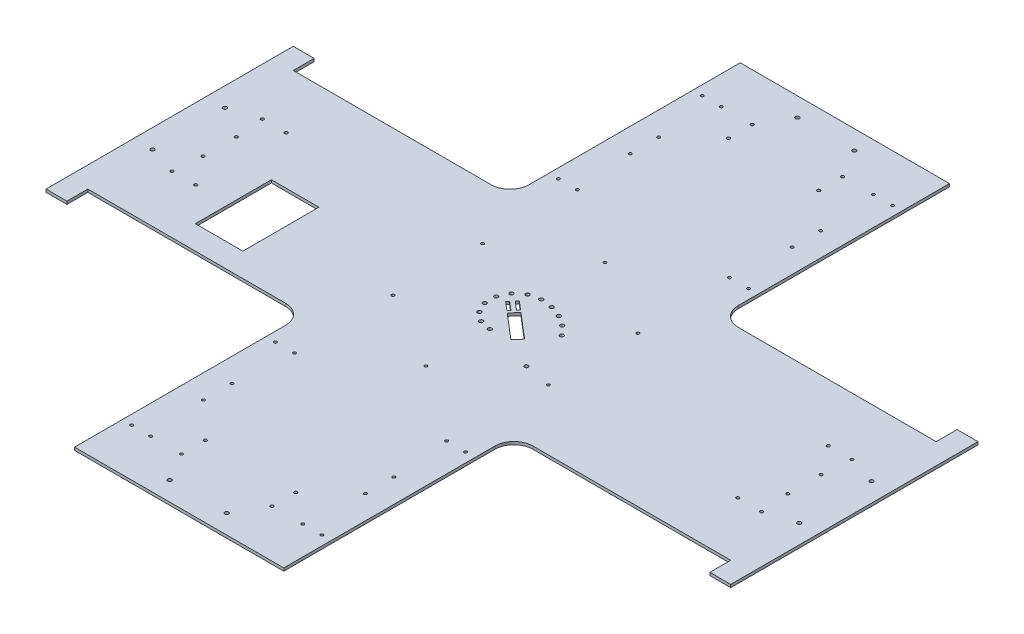
SolidWorks part; units mm, degrees
ref_plane "Front Plane" through (0, 0, 0) normal (0, 0, 1) x (1, 0, 0)
ref_plane "Top Plane" through (0, 0, 0) normal (0, 1, 0) x (1, 0, 0)
ref_plane "Right Plane" through (0, 0, 0) normal (1, 0, 0) x (0, 0, -1)
sketch "Sketch1" plane through (0, 0, 0) normal (0, 1, 0) x (1, 0, 0)
  line L0 (-110, 350) -> (-110, 108)
  line L1 (-110, 108) -> (-338, 108)
  line L2 (-338, 108) -> (-338, 130)
  line L3 (-338, 130) -> (-360, 130)
  line L4 (-360, 130) -> (-360, -130)
  line L5 (-360, 0) -> (1003.1457, 0) construction
  line L6 (0, 350) -> (0, -620.7989) construction
  line L7 (-338, -130) -> (-360, -130)
  line L8 (-338, -108) -> (-338, -130)
  line L9 (-110, -108) -> (-338, -108)
  line L10 (-110, 350) -> (110, 350)
  line L11 (-110, -350) -> (-110, -108)
  line L12 (-110, -350) -> (110, -350)
  line L13 (110, -350) -> (110, -108)
  line L14 (110, -108) -> (338, -108)
  line L15 (338, -108) -> (338, -130)
  line L16 (338, -130) -> (360, -130)
  line L17 (360, 130) -> (360, -130)
  line L18 (338, 130) -> (360, 130)
  line L19 (338, 108) -> (338, 130)
  line L20 (110, 108) -> (338, 108)
  line L21 (110, 350) -> (110, 108)
  point P17 (0, -350)
  dimension "D1" = 110
  dimension "D2" = 22
  dimension "D3" = 22
  dimension "D4" = 242
  dimension "D5" = 130
  dimension "D6" = 250
  dimension "D7" = 110
  dimension "D8" = 108
extrude "Boss-Extrude1" add sketch "Sketch1" along normal blind 3
sketch "Sketch2" plane through (0, 3, 0) normal (0, 1, 0) x (1, 0, 0)
  line L0 (360, -130) -> (360, 130) construction
  line L2 (338, 108) -> (110, 108) construction
  line L4 (0, 107.9437) -> (0, -458.275) construction
  line L5 (110, 108) -> (110, 350) construction
  line L6 (110, 350) -> (-110, 350) construction
  line L7 (-540.1841, 0) -> (-80.3508, 0) construction
  circle A0 centre (310, 47.5) radius 1.6
  circle A1 centre (285, 47.5) radius 1.6
  circle A2 centre (307.5, 17.5) radius 1.6
  circle A3 centre (307.5, -17.5) radius 1.6
  circle A4 centre (310, -47.5) radius 1.6
  circle A5 centre (285, -47.5) radius 1.6
  circle A6 centre (-285, -47.5) radius 1.6
  circle A7 centre (-310, -47.5) radius 1.6
  circle A8 centre (-307.5, -17.5) radius 1.6
  circle A9 centre (-307.5, 17.5) radius 1.6
  circle A10 centre (-285, 47.5) radius 1.6
  circle A11 centre (-310, 47.5) radius 1.6
  circle A13 centre (47.5, 300) radius 1.6
  circle A15 centre (47.5, 275) radius 1.6
  circle A16 centre (-47.5, 275) radius 1.6
  circle A17 centre (-47.5, 300) radius 1.6
  circle A18 centre (-47.5, -300) radius 1.6
  circle A19 centre (-47.5, -275) radius 1.6
  circle A20 centre (47.5, -275) radius 1.6
  circle A21 centre (47.5, -300) radius 1.6
  dimension "D1" = 3.2
  dimension "D2" = 3.2
  dimension "D3" = 3.2
  dimension "D4" = 3.2
  dimension "D5" = 3.2
  dimension "D6" = 3.2
  dimension "D15" = 3.2
  dimension "D16" = 3.2
  dimension "D7" = 50
  dimension "D8" = 25
  dimension "D9" = 95
  dimension "D10" = 35
  dimension "D11" = 60.5
  dimension "D12" = 90.5
  dimension "D13" = 52.5
  dimension "D14" = 110
  dimension "D17" = 50
  dimension "D18" = 25
  dimension "D19" = 62.5
  dimension "D20" = 108
extrude "Cut-Extrude1" cut sketch "Sketch2" against normal through all
sketch "Sketch3" plane through (0, 3, 0) normal (0, 1, 0) x (1, 0, 0)
  line L0 (360, -130) -> (360, 130) construction
  line L1 (338, 108) -> (110, 108) construction
  line L2 (-553.4456, 0) -> (-91.4299, 0) construction
  line L3 (0, 286.895) -> (0, -255.8046) construction
  line L4 (110, 108) -> (110, 350) construction
  line L5 (110, 350) -> (-110, 350) construction
  line L6 (-110, 350) -> (-110, 108) construction
  circle A0 centre (340, 38) radius 2
  circle A2 centre (340, -38) radius 2
  circle A3 centre (-340, -38) radius 2
  circle A4 centre (-340, 38) radius 2
  circle A5 centre (-30, 330) radius 2
  circle A7 centre (30, 330) radius 2
  circle A8 centre (30, -330) radius 2
  circle A9 centre (-30, -330) radius 2
  dimension "D1" = 4
  dimension "D6" = 4
  dimension "D7" = 80
  dimension "D2" = 20
  dimension "D3" = 70
  dimension "D4" = 108
  dimension "D5" = 110
  dimension "D8" = 20
extrude "Cut-Extrude2" cut sketch "Sketch3" against normal through all
sketch "Sketch4" plane through (0, 3, 0) normal (0, 1, 0) x (1, 0, 0)
  line L0 (0.8085, 29.8301) -> (-10.8593, 27.1789) construction
  line L1 (-10.8593, 27.1789) -> (-20.2814, 19.6888) construction
  line L2 (-20.2814, 19.6888) -> (-25.5122, 8.8484) construction
  line L3 (-25.5122, 8.8484) -> (-25.5122, -3.1881) construction
  line L4 (-25.5122, -3.1881) -> (-20.2814, -14.0285) construction
  line L5 (-20.2814, -14.0285) -> (-10.8593, -21.5186) construction
  line L6 (-10.8593, -21.5186) -> (0.8815, -24.1698) construction
  line L7 (0.8085, 29.8301) -> (13.3461, 28.3304) construction
  line L8 (13.3461, 28.3304) -> (25.203, 23.9881) construction
  line L9 (25.203, 23.9881) -> (35.7602, 17.0608) construction
  line L10 (35.7602, 17.0608) -> (44.4635, 7.9124) construction
  line L11 (44.4635, 7.9124) -> (53.9283, -38.7532) construction
  line L12 (0.8085, 2.8301) -> (0.8085, 97.0801) construction
  line L13 (0.8085, 2.8301) -> (0.8085, 97.0801) construction
  line L14 (0.8085, 2.8301) -> (82.4314, 49.9551) construction
  line L15 (-4.5918, -0.4234) -> (21.6669, -22.8005)
  line L16 (21.6669, -22.8005) -> (28.2827, -15.037)
  line L17 (-4.5918, -0.4234) -> (2.0241, 7.3401)
  line L18 (2.0241, 7.3401) -> (28.2827, -15.037)
  line L19 (-6.8751, 1.5225) -> (-4.9293, 3.8058)
  line L20 (-4.9293, 3.8058) -> (-14.0627, 11.5892)
  line L21 (-14.0627, 11.5892) -> (-16.0085, 9.3058)
  line L22 (-16.0085, 9.3058) -> (-6.8751, 1.5225)
  line L23 (2.0241, 7.3401) -> (0.8085, 2.8301) construction
  line L24 (-2.2051, 7.0025) -> (-0.2593, 9.2859)
  line L25 (-0.2593, 9.2859) -> (-9.3927, 17.0692)
  line L26 (-9.3927, 17.0692) -> (-11.3385, 14.7859)
  line L27 (-11.3385, 14.7859) -> (-2.2051, 7.0025)
  line L28 (0.8085, 2.8301) -> (48.4037, 2.8301) construction
  line L29 (0.8085, 2.8301) -> (0.8085, -17.1699) construction
  circle A0 centre (0.8085, 29.8301) radius 2
  circle A1 centre (13.3461, 28.3304) radius 2
  circle A2 centre (25.203, 23.9881) radius 2
  circle A3 centre (35.7602, 17.0608) radius 2
  circle A4 centre (44.4635, 7.9124) radius 2
  circle A5 centre (53.9283, -38.7532) radius 2
  circle A6 centre (0.8085, 2.8301) radius 135 construction
  circle A7 centre (-10.8593, 27.1789) radius 2
  circle A8 centre (-20.2814, 19.6888) radius 2
  circle A9 centre (-25.5122, 8.8484) radius 2
  circle A10 centre (-25.5122, -3.1881) radius 2
  circle A11 centre (-20.2814, -14.0285) radius 2
  circle A12 centre (-10.8593, -21.5186) radius 2
  circle A13 centre (0.8815, -24.1698) radius 2
  circle A14 centre (0.8085, 2.8301) radius 27 construction
  circle A15 centre (0.8085, 2.8301) radius 28.4158 construction
  circle A16 centre (0.8085, 2.8301) radius 32.2916 construction
  circle A17 centre (0.8085, 2.8301) radius 37.7377 construction
  circle A18 centre (0.8085, 2.8301) radius 43.9498 construction
  circle A19 centre (0.8085, 2.8301) radius 67.4602 construction
  circle A20 centre (0.8085, 2.8301) radius 94.25 construction
  circle A21 centre (0.8085, 97.0801) radius 1.5
  circle A22 centre (82.4314, 49.9551) radius 1.5
  circle A23 centre (82.4314, -44.2949) radius 1.5
  circle A24 centre (0.8085, -91.4199) radius 1.5
  circle A25 centre (-80.8144, -44.2949) radius 1.5
  circle A26 centre (-80.8144, 49.9551) radius 1.5
  point P32 (0.8085, 2.8301)
  dimension "D1" = 4
  dimension "D2" = 270
  dimension "D3" = 54
  dimension "D12" = 188.5
  dimension "D13" = 3
  dimension "D4" = 11.9653
  dimension "D5" = 12.627
  dimension "D6" = 47.6157
  dimension "D8" = 60.7074
  dimension "D9" = 70.0293
  dimension "D10" = 81.6875
  dimension "D14" = 60
  dimension "D15" = 34.5
  dimension "D16" = 10.2
  dimension "D17" = 12
  dimension "D18" = 3
  dimension "D19" = 3
  dimension "D20" = 4.6709
  dimension "D21" = 3
  dimension "D22" = 20
  dimension "D23" = 130.437
  dimension "D24" = 5.4003
extrude "Cut-Extrude3" cut sketch "Sketch4" against normal blind 10
sketch "Sketch5" plane through (0, 3, 0) normal (0, 1, 0) x (1, 0, 0)
  line L0 (110, 350) -> (-110, 350) construction
  line L1 (110, 108) -> (110, 350) construction
  line L2 (0, 224.365) -> (185.6725, 224.365) construction
  line L3 (90, 361.0488) -> (90, 126.2188) construction
  line L4 (0, 375.894) -> (0, 88.4107) construction
  line L5 (349.7475, 0) -> (-242.2654, 0) construction
  circle A0 centre (80, 300) radius 1.5
  circle A1 centre (80, 148.73) radius 1.5
  circle A2 centre (85.11, 239.365) radius 1.5
  circle A3 centre (85.11, 209.365) radius 1.5
  circle A4 centre (100, 148.73) radius 1.5
  circle A5 centre (100, 300) radius 1.5
  circle A6 centre (-100, 300) radius 1.5
  circle A7 centre (-100, 148.73) radius 1.5
  circle A8 centre (-85.11, 209.365) radius 1.5
  circle A9 centre (-85.11, 239.365) radius 1.5
  circle A10 centre (-80, 148.73) radius 1.5
  circle A11 centre (-80, 300) radius 1.5
  circle A12 centre (-80, -300) radius 1.5
  circle A13 centre (-80, -148.73) radius 1.5
  circle A14 centre (-85.11, -239.365) radius 1.5
  circle A15 centre (-85.11, -209.365) radius 1.5
  circle A16 centre (-100, -148.73) radius 1.5
  circle A17 centre (-100, -300) radius 1.5
  circle A18 centre (100, -300) radius 1.5
  circle A19 centre (100, -148.73) radius 1.5
  circle A20 centre (85.11, -209.365) radius 1.5
  circle A21 centre (85.11, -239.365) radius 1.5
  circle A22 centre (80, -148.73) radius 1.5
  circle A23 centre (80, -300) radius 1.5
  dimension "D1" = 3
  dimension "D2" = 3
  dimension "D6" = 3
  dimension "D7" = 3
  dimension "D3" = 151.27
  dimension "D4" = 50
  dimension "D5" = 5.11
  dimension "30" = 30
  dimension "D8" = 30
  dimension "D9" = 75.635
  dimension "D10" = 15
  dimension "D11" = 10
extrude "Cut-Extrude4" cut sketch "Sketch5" against normal blind 10
fillet "Fillet1" radius 20 4 edges at (110, 1.5, -108) (-110, 1.5, -108) (-110, 1.5, 108) (110, 1.5, 108)
sketch "Sketch6" plane through (0, 3, 0) normal (0, 1, 0) x (1, 0, 0)
  line L1 (-245.8442, -3.7297) -> (-196.6878, -3.7297)
  line L2 (-245.8442, -3.7297) -> (-245.8442, -89.096)
  line L3 (-245.8442, -89.096) -> (-196.6878, -89.096)
  line L4 (-196.6878, -3.7297) -> (-196.6878, -89.096)
sketch "Sketch7" plane through (0, 3, 0) normal (0, 1, 0) x (1, 0, 0)
  line L0 (-338, -108) -> (-130, -108) construction
  line L1 (-250, -3) -> (-200, -3)
  line L2 (-250, -3) -> (-250, -83)
  line L3 (-250, -83) -> (-200, -83)
  line L4 (-200, -3) -> (-200, -83)
  line L5 (-360, 130) -> (-360, -130) construction
  dimension "D1" = 80
  dimension "D2" = 50
  dimension "D3" = 25
  dimension "D4" = 110
extrude "Cut-Extrude5" cut sketch "Sketch7" against normal blind 10
equation "\"M3\"= 3.2mm"
equation "\"D1@Sketch2\"=\"M3\""
equation "\"D2@Sketch2\"=\"M3\""
equation "\"D3@Sketch2\"=\"M3\""
equation "\"D4@Sketch2\"=\"M3\""
equation "\"D5@Sketch2\"=\"M3\""
equation "\"D6@Sketch2\"=\"M3\""
equation "\"D15@Sketch2\"=\"M3\""
equation "\"D16@Sketch2\"=\"M3\""
